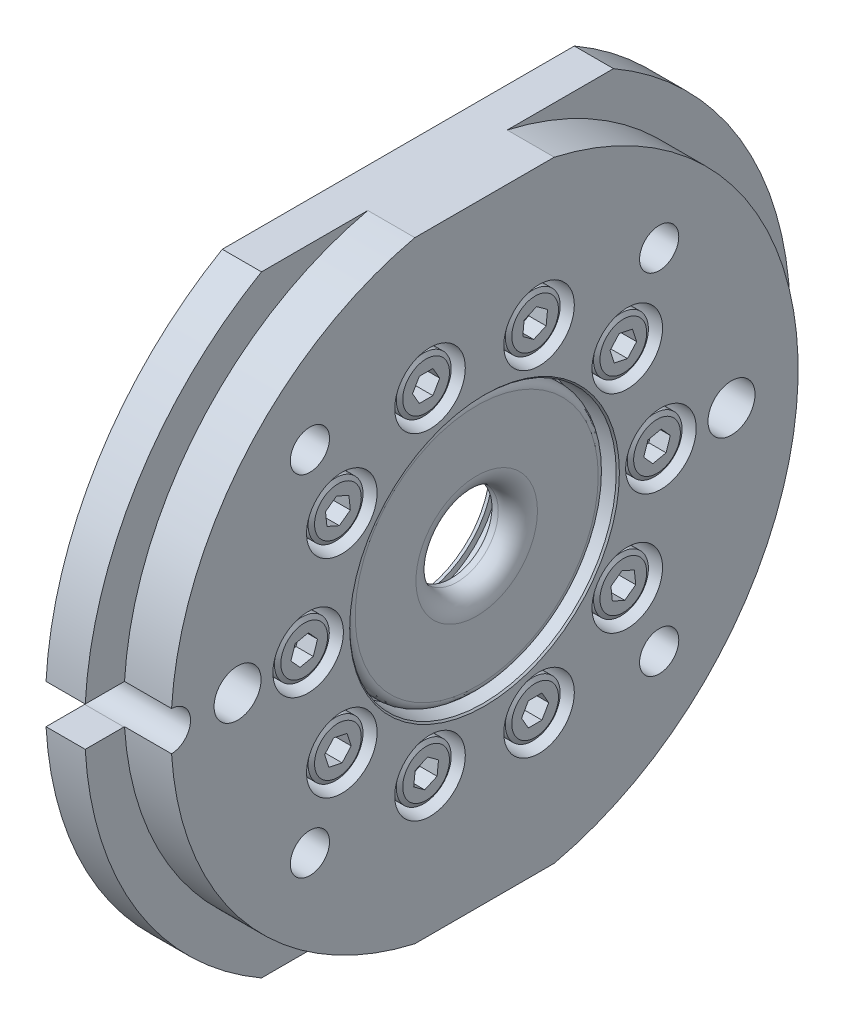
SolidWorks part; units mm, degrees
ref_plane "正面" through (0, 0, 0) normal (0, 0, 1) x (1, 0, 0)
ref_plane "平面" through (0, 0, 0) normal (0, 1, 0) x (1, 0, 0)
ref_plane "右側面" through (0, 0, 0) normal (1, 0, 0) x (0, 0, -1)
ref_plane "平面1" through (503, 0, 0) normal (1, 0, 0) x (0, 0, -1)
sketch "ｽｹｯﾁ1" plane through (503, 0, 0) normal (1, 0, 0) x (0, 0, -1)
  line L0 (-8.8882, 600.5) -> (22.4499, 600.5)
  line L1 (22.4499, 678.5) -> (-8.8882, 678.5)
  arc A0 (22.4499, 600.5) -> (22.4499, 678.5) centre (0, 639.5) ccw
  arc A1 (-8.8882, 678.5) -> (-39.9219, 641.9988) centre (0, 639.5) ccw
  arc A2 (-39.9219, 641.9988) -> (-39.9219, 637.0012) centre (-40, 639.5) cw
  arc A3 (-39.9219, 637.0012) -> (-8.8882, 600.5) centre (0, 639.5) ccw
extrude "ﾎﾞｽ - 押し出し1" add sketch "ｽｹｯﾁ1" against normal blind 6
sketch "ｽｹｯﾁ2" plane through (497, 0, 0) normal (-1, 0, 0) x (0, 0, 1)
  line L0 (-22.4499, 678.5) -> (22.4499, 678.5)
  line L1 (44.9305, 642) -> (40, 642)
  line L2 (40, 637) -> (44.9305, 637)
  line L3 (22.4499, 600.5) -> (-22.4499, 600.5)
  arc A0 (22.4499, 678.5) -> (44.9305, 642) centre (0, 639.5) cw
  arc A1 (40, 642) -> (40, 637) centre (40, 639.5) ccw
  arc A2 (44.9305, 637) -> (22.4499, 600.5) centre (0, 639.5) cw
  arc A3 (-22.4499, 600.5) -> (-22.4499, 678.5) centre (0, 639.5) cw
extrude "ﾎﾞｽ - 押し出し2" add sketch "ｽｹｯﾁ2" along normal blind 5
sketch "ｽｹｯﾁ3" plane through (503, 0, 0) normal (1, 0, 0) x (0, 0, -1)
  line L0 (8.8882, 600.5) -> (22.4499, 600.5)
  line L1 (22.4499, 678.5) -> (8.8882, 678.5)
  arc A0 (8.8882, 678.5) -> (8.8882, 600.5) centre (0, 639.5) cw
  arc A1 (22.4499, 600.5) -> (22.4499, 678.5) centre (0, 639.5) ccw
extrude "ｶｯﾄ - 押し出し1" cut sketch "ｽｹｯﾁ3" against normal blind 6
hole_wizard "M33 ﾍﾘｺｲﾙ用ねじ下穴ﾄﾞﾘﾙ1" positions "ｽｹｯﾁ5" profile "ｽｹｯﾁ4" hole size "M33x3.5" standard "Ansi Metric"
sketch "ｽｹｯﾁ5" plane through (503, 0, 0) normal (1, 0, 0) x (0, 0, -1)
  point P0 (0, 639.5)
sketch "ｽｹｯﾁ4" plane through (503, 639.5, 0) normal (0, 1, 0) x (0, 0, -1)
  line L0 (0, 0) -> (0, 4.5)
  line L1 (0, 4.5) -> (17, 4.5)
  line L2 (17, 4.5) -> (17, 0)
  line L5 (17, 0) -> (0, 0)
  line L10 (0, 4.5) -> (-17, 4.5) construction
  line L11 (0, -6.35) -> (0, 107.95) construction
  dimension "穴の直径" = 34
  dimension "穴の深さ" = 4.5
  dimension "ﾄﾞﾘﾙ角度" = 180
sketch "ｽｹｯﾁ6" plane through (498.5, 0, 0) normal (1, 0, 0) x (0, 0, -1)
  circle A0 centre (0, 639.5) radius 16.5
extrude "ﾎﾞｽ - 押し出し3" add sketch "ｽｹｯﾁ6" along normal blind 3.5
ref_plane "平面2" through (494.4, 0, 0) normal (-1, 0, 0) x (0, -1, 0)
sketch "ｽｹｯﾁ7" plane through (494.4, 0, 0) normal (-1, 0, 0) x (0, -1, 0)
  circle A0 centre (-639.5, 0) radius 10.5
extrude "ｶｯﾄ - 押し出し2" cut sketch "ｽｹｯﾁ7" against normal blind 4.1
sketch "ｽｹｯﾁ8" plane through (498.5, 0, 0) normal (-1, 0, 0) x (0, 0, 1)
  circle A0 centre (0, 639.5) radius 9.7
extrude "ｶｯﾄ - 押し出し3" cut sketch "ｽｹｯﾁ8" against normal blind 0.2
sketch "ｽｹｯﾁ9" plane through (502, 0, 0) normal (1, 0, 0) x (0, 0, -1)
  circle A0 centre (0, 639.5) radius 5.25
extrude "ｶｯﾄ - 押し出し4" cut sketch "ｽｹｯﾁ9" against normal up to next
hole_wizard "M48 すきま穴1" positions "ｽｹｯﾁ11" profile "ｽｹｯﾁ10" hole size "M48" standard "Ansi Metric"
sketch "ｽｹｯﾁ11" plane through (492, 0, 0) normal (-1, 0, 0) x (0, 0, 1)
  point P0 (0, 639.5)
sketch "ｽｹｯﾁ10" plane through (492, 639.5, 0) normal (0, 1, 0) x (0, 0, 1)
  line L0 (0, 0) -> (0, 2)
  line L1 (0, 2) -> (27.5, 2)
  line L2 (27.5, 2) -> (27.5, 0)
  line L5 (27.5, 0) -> (0, 0)
  line L10 (0, 2) -> (-27.5, 2) construction
  line L11 (0, -6.35) -> (0, 107.95) construction
  dimension "穴の直径" = 55
  dimension "穴の深さ" = 2
  dimension "ﾄﾞﾘﾙ角度" = 180
sketch "ｽｹｯﾁ12" plane through (494, 0, 0) normal (-1, 0, 0) x (0, 0, 1)
  circle A0 centre (0, 639.5) radius 9.7
extrude "ｶｯﾄ - 押し出し5" cut sketch "ｽｹｯﾁ12" against normal up to next
hole_wizard "Ø9.0 (9) 直径の穴1" positions "ｽｹｯﾁ14" profile "ｽｹｯﾁ13" hole size "Ø9.0" standard "Ansi Metric"
sketch "ｽｹｯﾁ14" plane through (503, 0, 0) normal (1, 0, 0) x (0, 0, -1)
  point P0 (6.9529, 618.1012)
sketch "ｽｹｯﾁ13" plane through (503, 618.1012, -6.9529) normal (0, 1, 0) x (0, 0, -1)
  line L0 (0, 0) -> (0, 5)
  line L1 (0, 5) -> (4.5, 5)
  line L2 (4.5, 5) -> (4.5, 0)
  line L5 (4.5, 0) -> (0, 0)
  line L10 (0, 5) -> (-4.5, 5) construction
  line L11 (0, -6.35) -> (0, 107.95) construction
  dimension "穴の直径" = 9
  dimension "穴の深さ" = 5
  dimension "ﾄﾞﾘﾙ角度" = 180
sketch "ｽｹｯﾁ15" plane through (498, 0, 0) normal (1, 0, 0) x (0, 0, -1)
  circle A0 centre (6.9529, 618.1012) radius 3.75
extrude "ﾎﾞｽ - 押し出し4" add sketch "ｽｹｯﾁ15" along normal blind 0.5
sketch "ｽｹｯﾁ16" plane through (498.5, 0, 0) normal (1, 0, 0) x (0, 0, -1)
  circle A0 centre (6.9529, 618.1012) radius 3.5
extrude "ﾎﾞｽ - 押し出し5" add sketch "ｽｹｯﾁ16" along normal blind 4
sketch "ｽｹｯﾁ17" plane through (502.5, 0, 0) normal (1, 0, 0) x (0, 0, -1)
  line L0 (8.6849, 618.1012) -> (7.8189, 619.6012)
  line L1 (7.8189, 619.6012) -> (6.0869, 619.6012)
  line L2 (6.0869, 619.6012) -> (5.2208, 618.1012)
  line L3 (5.2208, 618.1012) -> (6.0869, 616.6012)
  line L4 (6.0869, 616.6012) -> (7.8189, 616.6012)
  line L5 (7.8189, 616.6012) -> (8.6849, 618.1012)
extrude "ｶｯﾄ - 押し出し6" cut sketch "ｽｹｯﾁ17" against normal blind 2.2
hole_wizard "Ø9.0 (9) 直径の穴2" positions "ｽｹｯﾁ19" profile "ｽｹｯﾁ18" hole size "Ø9.0" standard "Ansi Metric"
sketch "ｽｹｯﾁ19" plane through (503, 0, 0) normal (1, 0, 0) x (0, 0, -1)
  point P0 (18.2029, 626.2748)
sketch "ｽｹｯﾁ18" plane through (503, 626.2748, -18.2029) normal (0, 1, 0) x (0, 0, -1)
  line L0 (0, 0) -> (0, 5)
  line L1 (0, 5) -> (4.5, 5)
  line L2 (4.5, 5) -> (4.5, 0)
  line L5 (4.5, 0) -> (0, 0)
  line L10 (0, 5) -> (-4.5, 5) construction
  line L11 (0, -6.35) -> (0, 107.95) construction
  dimension "穴の直径" = 9
  dimension "穴の深さ" = 5
  dimension "ﾄﾞﾘﾙ角度" = 180
sketch "ｽｹｯﾁ20" plane through (498, 0, 0) normal (1, 0, 0) x (0, 0, -1)
  circle A0 centre (18.2029, 626.2748) radius 3.75
extrude "ﾎﾞｽ - 押し出し6" add sketch "ｽｹｯﾁ20" along normal blind 0.5
sketch "ｽｹｯﾁ21" plane through (498.5, 0, 0) normal (1, 0, 0) x (0, 0, -1)
  circle A0 centre (18.2029, 626.2748) radius 3.5
extrude "ﾎﾞｽ - 押し出し7" add sketch "ｽｹｯﾁ21" along normal blind 4
sketch "ｽｹｯﾁ22" plane through (502.5, 0, 0) normal (1, 0, 0) x (0, 0, -1)
  line L0 (19.6041, 627.2929) -> (18.0218, 627.9974)
  line L1 (18.0218, 627.9974) -> (16.6206, 626.9793)
  line L2 (16.6206, 626.9793) -> (16.8016, 625.2568)
  line L3 (16.8016, 625.2568) -> (18.3839, 624.5523)
  line L4 (18.3839, 624.5523) -> (19.7852, 625.5703)
  line L5 (19.7852, 625.5703) -> (19.6041, 627.2929)
extrude "ｶｯﾄ - 押し出し7" cut sketch "ｽｹｯﾁ22" against normal blind 2.2
hole_wizard "Ø9.0 (9) 直径の穴3" positions "ｽｹｯﾁ24" profile "ｽｹｯﾁ23" hole size "Ø9.0" standard "Ansi Metric"
sketch "ｽｹｯﾁ24" plane through (503, 0, 0) normal (1, 0, 0) x (0, 0, -1)
  point P0 (22.5, 639.5)
sketch "ｽｹｯﾁ23" plane through (503, 639.5, -22.5) normal (0, 1, 0) x (0, 0, -1)
  line L0 (0, 0) -> (0, 5)
  line L1 (0, 5) -> (4.5, 5)
  line L2 (4.5, 5) -> (4.5, 0)
  line L5 (4.5, 0) -> (0, 0)
  line L10 (0, 5) -> (-4.5, 5) construction
  line L11 (0, -6.35) -> (0, 107.95) construction
  dimension "穴の直径" = 9
  dimension "穴の深さ" = 5
  dimension "ﾄﾞﾘﾙ角度" = 180
sketch "ｽｹｯﾁ25" plane through (498, 0, 0) normal (1, 0, 0) x (0, 0, -1)
  circle A0 centre (22.5, 639.5) radius 3.75
extrude "ﾎﾞｽ - 押し出し8" add sketch "ｽｹｯﾁ25" along normal blind 0.5
sketch "ｽｹｯﾁ26" plane through (498.5, 0, 0) normal (1, 0, 0) x (0, 0, -1)
  circle A0 centre (22.5, 639.5) radius 3.5
extrude "ﾎﾞｽ - 押し出し9" add sketch "ｽｹｯﾁ26" along normal blind 4
sketch "ｽｹｯﾁ27" plane through (502.5, 0, 0) normal (1, 0, 0) x (0, 0, -1)
  line L0 (23.0352, 641.1473) -> (21.341, 640.7872)
  line L1 (21.341, 640.7872) -> (20.8058, 639.1399)
  line L2 (20.8058, 639.1399) -> (21.9648, 637.8527)
  line L3 (21.9648, 637.8527) -> (23.659, 638.2128)
  line L4 (23.659, 638.2128) -> (24.1942, 639.8601)
  line L5 (24.1942, 639.8601) -> (23.0352, 641.1473)
extrude "ｶｯﾄ - 押し出し8" cut sketch "ｽｹｯﾁ27" against normal blind 2.2
hole_wizard "Ø9.0 (9) 直径の穴4" positions "ｽｹｯﾁ29" profile "ｽｹｯﾁ28" hole size "Ø9.0" standard "Ansi Metric"
sketch "ｽｹｯﾁ29" plane through (503, 0, 0) normal (1, 0, 0) x (0, 0, -1)
  point P0 (18.2029, 652.7252)
sketch "ｽｹｯﾁ28" plane through (503, 652.7252, -18.2029) normal (0, 1, 0) x (0, 0, -1)
  line L0 (0, 0) -> (0, 5)
  line L1 (0, 5) -> (4.5, 5)
  line L2 (4.5, 5) -> (4.5, 0)
  line L5 (4.5, 0) -> (0, 0)
  line L10 (0, 5) -> (-4.5, 5) construction
  line L11 (0, -6.35) -> (0, 107.95) construction
  dimension "穴の直径" = 9
  dimension "穴の深さ" = 5
  dimension "ﾄﾞﾘﾙ角度" = 180
sketch "ｽｹｯﾁ30" plane through (498, 0, 0) normal (1, 0, 0) x (0, 0, -1)
  circle A0 centre (18.2029, 652.7252) radius 3.75
extrude "ﾎﾞｽ - 押し出し10" add sketch "ｽｹｯﾁ30" along normal blind 0.5
sketch "ｽｹｯﾁ31" plane through (498.5, 0, 0) normal (1, 0, 0) x (0, 0, -1)
  circle A0 centre (18.2029, 652.7252) radius 3.5
extrude "ﾎﾞｽ - 押し出し11" add sketch "ｽｹｯﾁ31" along normal blind 4
sketch "ｽｹｯﾁ32" plane through (502.5, 0, 0) normal (1, 0, 0) x (0, 0, -1)
  line L0 (17.6676, 654.3724) -> (16.5087, 653.0853)
  line L1 (16.5087, 653.0853) -> (17.0439, 651.438)
  line L2 (17.0439, 651.438) -> (18.7381, 651.0779)
  line L3 (18.7381, 651.0779) -> (19.8971, 652.3651)
  line L4 (19.8971, 652.3651) -> (19.3619, 654.0123)
  line L5 (19.3619, 654.0123) -> (17.6676, 654.3724)
extrude "ｶｯﾄ - 押し出し9" cut sketch "ｽｹｯﾁ32" against normal blind 2.2
hole_wizard "Ø9.0 (9) 直径の穴5" positions "ｽｹｯﾁ34" profile "ｽｹｯﾁ33" hole size "Ø9.0" standard "Ansi Metric"
sketch "ｽｹｯﾁ34" plane through (503, 0, 0) normal (1, 0, 0) x (0, 0, -1)
  point P0 (6.9529, 660.8988)
sketch "ｽｹｯﾁ33" plane through (503, 660.8988, -6.9529) normal (0, 1, 0) x (0, 0, -1)
  line L0 (0, 0) -> (0, 5)
  line L1 (0, 5) -> (4.5, 5)
  line L2 (4.5, 5) -> (4.5, 0)
  line L5 (4.5, 0) -> (0, 0)
  line L10 (0, 5) -> (-4.5, 5) construction
  line L11 (0, -6.35) -> (0, 107.95) construction
  dimension "穴の直径" = 9
  dimension "穴の深さ" = 5
  dimension "ﾄﾞﾘﾙ角度" = 180
sketch "ｽｹｯﾁ35" plane through (498, 0, 0) normal (1, 0, 0) x (0, 0, -1)
  circle A0 centre (6.9529, 660.8988) radius 3.75
extrude "ﾎﾞｽ - 押し出し12" add sketch "ｽｹｯﾁ35" along normal blind 0.5
sketch "ｽｹｯﾁ36" plane through (498.5, 0, 0) normal (1, 0, 0) x (0, 0, -1)
  circle A0 centre (6.9529, 660.8988) radius 3.5
extrude "ﾎﾞｽ - 押し出し13" add sketch "ｽｹｯﾁ36" along normal blind 4
sketch "ｽｹｯﾁ37" plane through (502.5, 0, 0) normal (1, 0, 0) x (0, 0, -1)
  line L0 (5.5516, 661.9168) -> (5.3706, 660.1943)
  line L1 (5.3706, 660.1943) -> (6.7718, 659.1762)
  line L2 (6.7718, 659.1762) -> (8.3541, 659.8807)
  line L3 (8.3541, 659.8807) -> (8.5352, 661.6033)
  line L4 (8.5352, 661.6033) -> (7.1339, 662.6213)
  line L5 (7.1339, 662.6213) -> (5.5516, 661.9168)
extrude "ｶｯﾄ - 押し出し10" cut sketch "ｽｹｯﾁ37" against normal blind 2.2
hole_wizard "Ø9.0 (9) 直径の穴6" positions "ｽｹｯﾁ39" profile "ｽｹｯﾁ38" hole size "Ø9.0" standard "Ansi Metric"
sketch "ｽｹｯﾁ39" plane through (503, 0, 0) normal (1, 0, 0) x (0, 0, -1)
  point P0 (-6.9529, 660.8988)
sketch "ｽｹｯﾁ38" plane through (503, 660.8988, 6.9529) normal (0, 1, 0) x (0, 0, -1)
  line L0 (0, 0) -> (0, 5)
  line L1 (0, 5) -> (4.5, 5)
  line L2 (4.5, 5) -> (4.5, 0)
  line L5 (4.5, 0) -> (0, 0)
  line L10 (0, 5) -> (-4.5, 5) construction
  line L11 (0, -6.35) -> (0, 107.95) construction
  dimension "穴の直径" = 9
  dimension "穴の深さ" = 5
  dimension "ﾄﾞﾘﾙ角度" = 180
sketch "ｽｹｯﾁ40" plane through (498, 0, 0) normal (1, 0, 0) x (0, 0, -1)
  circle A0 centre (-6.9529, 660.8988) radius 3.75
extrude "ﾎﾞｽ - 押し出し14" add sketch "ｽｹｯﾁ40" along normal blind 0.5
sketch "ｽｹｯﾁ41" plane through (498.5, 0, 0) normal (1, 0, 0) x (0, 0, -1)
  circle A0 centre (-6.9529, 660.8988) radius 3.5
extrude "ﾎﾞｽ - 押し出し15" add sketch "ｽｹｯﾁ41" along normal blind 4
sketch "ｽｹｯﾁ42" plane through (502.5, 0, 0) normal (1, 0, 0) x (0, 0, -1)
  line L0 (-8.6849, 660.8988) -> (-7.8189, 659.3988)
  line L1 (-7.8189, 659.3988) -> (-6.0869, 659.3988)
  line L2 (-6.0869, 659.3988) -> (-5.2208, 660.8988)
  line L3 (-5.2208, 660.8988) -> (-6.0869, 662.3988)
  line L4 (-6.0869, 662.3988) -> (-7.8189, 662.3988)
  line L5 (-7.8189, 662.3988) -> (-8.6849, 660.8988)
extrude "ｶｯﾄ - 押し出し11" cut sketch "ｽｹｯﾁ42" against normal blind 2.2
hole_wizard "Ø9.0 (9) 直径の穴7" positions "ｽｹｯﾁ44" profile "ｽｹｯﾁ43" hole size "Ø9.0" standard "Ansi Metric"
sketch "ｽｹｯﾁ44" plane through (503, 0, 0) normal (1, 0, 0) x (0, 0, -1)
  point P0 (-18.2029, 652.7252)
sketch "ｽｹｯﾁ43" plane through (503, 652.7252, 18.2029) normal (0, 1, 0) x (0, 0, -1)
  line L0 (0, 0) -> (0, 5)
  line L1 (0, 5) -> (4.5, 5)
  line L2 (4.5, 5) -> (4.5, 0)
  line L5 (4.5, 0) -> (0, 0)
  line L10 (0, 5) -> (-4.5, 5) construction
  line L11 (0, -6.35) -> (0, 107.95) construction
  dimension "穴の直径" = 9
  dimension "穴の深さ" = 5
  dimension "ﾄﾞﾘﾙ角度" = 180
sketch "ｽｹｯﾁ45" plane through (498, 0, 0) normal (1, 0, 0) x (0, 0, -1)
  circle A0 centre (-18.2029, 652.7252) radius 3.75
extrude "ﾎﾞｽ - 押し出し16" add sketch "ｽｹｯﾁ45" along normal blind 0.5
sketch "ｽｹｯﾁ46" plane through (498.5, 0, 0) normal (1, 0, 0) x (0, 0, -1)
  circle A0 centre (-18.2029, 652.7252) radius 3.5
extrude "ﾎﾞｽ - 押し出し17" add sketch "ｽｹｯﾁ46" along normal blind 4
sketch "ｽｹｯﾁ47" plane through (502.5, 0, 0) normal (1, 0, 0) x (0, 0, -1)
  line L0 (-19.6041, 651.7071) -> (-18.0218, 651.0026)
  line L1 (-18.0218, 651.0026) -> (-16.6206, 652.0207)
  line L2 (-16.6206, 652.0207) -> (-16.8016, 653.7432)
  line L3 (-16.8016, 653.7432) -> (-18.3839, 654.4477)
  line L4 (-18.3839, 654.4477) -> (-19.7852, 653.4297)
  line L5 (-19.7852, 653.4297) -> (-19.6041, 651.7071)
extrude "ｶｯﾄ - 押し出し12" cut sketch "ｽｹｯﾁ47" against normal blind 2.2
hole_wizard "Ø9.0 (9) 直径の穴8" positions "ｽｹｯﾁ49" profile "ｽｹｯﾁ48" hole size "Ø9.0" standard "Ansi Metric"
sketch "ｽｹｯﾁ49" plane through (503, 0, 0) normal (1, 0, 0) x (0, 0, -1)
  point P0 (-22.5, 639.5)
sketch "ｽｹｯﾁ48" plane through (503, 639.5, 22.5) normal (0, 1, 0) x (0, 0, -1)
  line L0 (0, 0) -> (0, 5)
  line L1 (0, 5) -> (4.5, 5)
  line L2 (4.5, 5) -> (4.5, 0)
  line L5 (4.5, 0) -> (0, 0)
  line L10 (0, 5) -> (-4.5, 5) construction
  line L11 (0, -6.35) -> (0, 107.95) construction
  dimension "穴の直径" = 9
  dimension "穴の深さ" = 5
  dimension "ﾄﾞﾘﾙ角度" = 180
sketch "ｽｹｯﾁ50" plane through (498, 0, 0) normal (1, 0, 0) x (0, 0, -1)
  circle A0 centre (-22.5, 639.5) radius 3.75
extrude "ﾎﾞｽ - 押し出し18" add sketch "ｽｹｯﾁ50" along normal blind 0.5
sketch "ｽｹｯﾁ51" plane through (498.5, 0, 0) normal (1, 0, 0) x (0, 0, -1)
  circle A0 centre (-22.5, 639.5) radius 3.5
extrude "ﾎﾞｽ - 押し出し19" add sketch "ｽｹｯﾁ51" along normal blind 4
sketch "ｽｹｯﾁ52" plane through (502.5, 0, 0) normal (1, 0, 0) x (0, 0, -1)
  line L0 (-23.0352, 637.8527) -> (-21.341, 638.2128)
  line L1 (-21.341, 638.2128) -> (-20.8058, 639.8601)
  line L2 (-20.8058, 639.8601) -> (-21.9648, 641.1473)
  line L3 (-21.9648, 641.1473) -> (-23.659, 640.7872)
  line L4 (-23.659, 640.7872) -> (-24.1942, 639.1399)
  line L5 (-24.1942, 639.1399) -> (-23.0352, 637.8527)
extrude "ｶｯﾄ - 押し出し13" cut sketch "ｽｹｯﾁ52" against normal blind 2.2
hole_wizard "Ø9.0 (9) 直径の穴9" positions "ｽｹｯﾁ54" profile "ｽｹｯﾁ53" hole size "Ø9.0" standard "Ansi Metric"
sketch "ｽｹｯﾁ54" plane through (503, 0, 0) normal (1, 0, 0) x (0, 0, -1)
  point P0 (-18.2029, 626.2748)
sketch "ｽｹｯﾁ53" plane through (503, 626.2748, 18.2029) normal (0, 1, 0) x (0, 0, -1)
  line L0 (0, 0) -> (0, 5)
  line L1 (0, 5) -> (4.5, 5)
  line L2 (4.5, 5) -> (4.5, 0)
  line L5 (4.5, 0) -> (0, 0)
  line L10 (0, 5) -> (-4.5, 5) construction
  line L11 (0, -6.35) -> (0, 107.95) construction
  dimension "穴の直径" = 9
  dimension "穴の深さ" = 5
  dimension "ﾄﾞﾘﾙ角度" = 180
sketch "ｽｹｯﾁ55" plane through (498, 0, 0) normal (1, 0, 0) x (0, 0, -1)
  circle A0 centre (-18.2029, 626.2748) radius 3.75
extrude "ﾎﾞｽ - 押し出し20" add sketch "ｽｹｯﾁ55" along normal blind 0.5
sketch "ｽｹｯﾁ56" plane through (498.5, 0, 0) normal (1, 0, 0) x (0, 0, -1)
  circle A0 centre (-18.2029, 626.2748) radius 3.5
extrude "ﾎﾞｽ - 押し出し21" add sketch "ｽｹｯﾁ56" along normal blind 4
sketch "ｽｹｯﾁ57" plane through (502.5, 0, 0) normal (1, 0, 0) x (0, 0, -1)
  line L0 (-17.6676, 624.6276) -> (-16.5087, 625.9147)
  line L1 (-16.5087, 625.9147) -> (-17.0439, 627.562)
  line L2 (-17.0439, 627.562) -> (-18.7381, 627.9221)
  line L3 (-18.7381, 627.9221) -> (-19.8971, 626.6349)
  line L4 (-19.8971, 626.6349) -> (-19.3619, 624.9877)
  line L5 (-19.3619, 624.9877) -> (-17.6676, 624.6276)
extrude "ｶｯﾄ - 押し出し14" cut sketch "ｽｹｯﾁ57" against normal blind 2.2
hole_wizard "Ø9.0 (9) 直径の穴10" positions "ｽｹｯﾁ59" profile "ｽｹｯﾁ58" hole size "Ø9.0" standard "Ansi Metric"
sketch "ｽｹｯﾁ59" plane through (503, 0, 0) normal (1, 0, 0) x (0, 0, -1)
  point P0 (-6.9529, 618.1012)
sketch "ｽｹｯﾁ58" plane through (503, 618.1012, 6.9529) normal (0, 1, 0) x (0, 0, -1)
  line L0 (0, 0) -> (0, 5)
  line L1 (0, 5) -> (4.5, 5)
  line L2 (4.5, 5) -> (4.5, 0)
  line L5 (4.5, 0) -> (0, 0)
  line L10 (0, 5) -> (-4.5, 5) construction
  line L11 (0, -6.35) -> (0, 107.95) construction
  dimension "穴の直径" = 9
  dimension "穴の深さ" = 5
  dimension "ﾄﾞﾘﾙ角度" = 180
sketch "ｽｹｯﾁ60" plane through (498, 0, 0) normal (1, 0, 0) x (0, 0, -1)
  circle A0 centre (-6.9529, 618.1012) radius 3.75
extrude "ﾎﾞｽ - 押し出し22" add sketch "ｽｹｯﾁ60" along normal blind 0.5
sketch "ｽｹｯﾁ61" plane through (498.5, 0, 0) normal (1, 0, 0) x (0, 0, -1)
  circle A0 centre (-6.9529, 618.1012) radius 3.5
extrude "ﾎﾞｽ - 押し出し23" add sketch "ｽｹｯﾁ61" along normal blind 4
sketch "ｽｹｯﾁ62" plane through (502.5, 0, 0) normal (1, 0, 0) x (0, 0, -1)
  line L0 (-5.5516, 617.0832) -> (-5.3706, 618.8057)
  line L1 (-5.3706, 618.8057) -> (-6.7718, 619.8238)
  line L2 (-6.7718, 619.8238) -> (-8.3541, 619.1193)
  line L3 (-8.3541, 619.1193) -> (-8.5352, 617.3967)
  line L4 (-8.5352, 617.3967) -> (-7.1339, 616.3787)
  line L5 (-7.1339, 616.3787) -> (-5.5516, 617.0832)
extrude "ｶｯﾄ - 押し出し15" cut sketch "ｽｹｯﾁ62" against normal blind 2.2
hole_wizard "Ø4.3 (4.3) 直径の穴1" positions "ｽｹｯﾁ64" profile "ｽｹｯﾁ63" hole size "Ø4.3" standard "Ansi Metric"
sketch "ｽｹｯﾁ64" plane through (494, 0, 0) normal (-1, 0, 0) x (0, 0, 1)
  point P0 (-6.9529, 618.1012)
sketch "ｽｹｯﾁ63" plane through (494, 618.1012, -6.9529) normal (0, 1, 0) x (0, 0, 1)
  line L0 (0, 0) -> (0, 4.5)
  line L1 (0, 4.5) -> (2.15, 4.5)
  line L2 (2.15, 4.5) -> (2.15, 0)
  line L5 (2.15, 0) -> (0, 0)
  line L10 (0, 4.5) -> (-2.15, 4.5) construction
  line L11 (0, -6.35) -> (0, 107.95) construction
  dimension "穴の直径" = 4.3
  dimension "穴の深さ" = 4.5
  dimension "ﾄﾞﾘﾙ角度" = 180
hole_wizard "Ø4.3 (4.3) 直径の穴2" positions "ｽｹｯﾁ66" profile "ｽｹｯﾁ65" hole size "Ø4.3" standard "Ansi Metric"
sketch "ｽｹｯﾁ66" plane through (494, 0, 0) normal (-1, 0, 0) x (0, 0, 1)
  point P0 (-18.2029, 626.2748)
sketch "ｽｹｯﾁ65" plane through (494, 626.2748, -18.2029) normal (0, 1, 0) x (0, 0, 1)
  line L0 (0, 0) -> (0, 4.5)
  line L1 (0, 4.5) -> (2.15, 4.5)
  line L2 (2.15, 4.5) -> (2.15, 0)
  line L5 (2.15, 0) -> (0, 0)
  line L10 (0, 4.5) -> (-2.15, 4.5) construction
  line L11 (0, -6.35) -> (0, 107.95) construction
  dimension "穴の直径" = 4.3
  dimension "穴の深さ" = 4.5
  dimension "ﾄﾞﾘﾙ角度" = 180
hole_wizard "Ø4.3 (4.3) 直径の穴3" positions "ｽｹｯﾁ68" profile "ｽｹｯﾁ67" hole size "Ø4.3" standard "Ansi Metric"
sketch "ｽｹｯﾁ68" plane through (494, 0, 0) normal (-1, 0, 0) x (0, 0, 1)
  point P0 (-22.5, 639.5)
sketch "ｽｹｯﾁ67" plane through (494, 639.5, -22.5) normal (0, 1, 0) x (0, 0, 1)
  line L0 (0, 0) -> (0, 4.5)
  line L1 (0, 4.5) -> (2.15, 4.5)
  line L2 (2.15, 4.5) -> (2.15, 0)
  line L5 (2.15, 0) -> (0, 0)
  line L10 (0, 4.5) -> (-2.15, 4.5) construction
  line L11 (0, -6.35) -> (0, 107.95) construction
  dimension "穴の直径" = 4.3
  dimension "穴の深さ" = 4.5
  dimension "ﾄﾞﾘﾙ角度" = 180
hole_wizard "Ø4.3 (4.3) 直径の穴4" positions "ｽｹｯﾁ70" profile "ｽｹｯﾁ69" hole size "Ø4.3" standard "Ansi Metric"
sketch "ｽｹｯﾁ70" plane through (494, 0, 0) normal (-1, 0, 0) x (0, 0, 1)
  point P0 (-18.2029, 652.7252)
sketch "ｽｹｯﾁ69" plane through (494, 652.7252, -18.2029) normal (0, 1, 0) x (0, 0, 1)
  line L0 (0, 0) -> (0, 4.5)
  line L1 (0, 4.5) -> (2.15, 4.5)
  line L2 (2.15, 4.5) -> (2.15, 0)
  line L5 (2.15, 0) -> (0, 0)
  line L10 (0, 4.5) -> (-2.15, 4.5) construction
  line L11 (0, -6.35) -> (0, 107.95) construction
  dimension "穴の直径" = 4.3
  dimension "穴の深さ" = 4.5
  dimension "ﾄﾞﾘﾙ角度" = 180
hole_wizard "Ø4.3 (4.3) 直径の穴5" positions "ｽｹｯﾁ72" profile "ｽｹｯﾁ71" hole size "Ø4.3" standard "Ansi Metric"
sketch "ｽｹｯﾁ72" plane through (494, 0, 0) normal (-1, 0, 0) x (0, 0, 1)
  point P0 (-6.9529, 660.8988)
sketch "ｽｹｯﾁ71" plane through (494, 660.8988, -6.9529) normal (0, 1, 0) x (0, 0, 1)
  line L0 (0, 0) -> (0, 4.5)
  line L1 (0, 4.5) -> (2.15, 4.5)
  line L2 (2.15, 4.5) -> (2.15, 0)
  line L5 (2.15, 0) -> (0, 0)
  line L10 (0, 4.5) -> (-2.15, 4.5) construction
  line L11 (0, -6.35) -> (0, 107.95) construction
  dimension "穴の直径" = 4.3
  dimension "穴の深さ" = 4.5
  dimension "ﾄﾞﾘﾙ角度" = 180
hole_wizard "Ø4.3 (4.3) 直径の穴6" positions "ｽｹｯﾁ74" profile "ｽｹｯﾁ73" hole size "Ø4.3" standard "Ansi Metric"
sketch "ｽｹｯﾁ74" plane through (494, 0, 0) normal (-1, 0, 0) x (0, 0, 1)
  point P0 (6.9529, 660.8988)
sketch "ｽｹｯﾁ73" plane through (494, 660.8988, 6.9529) normal (0, 1, 0) x (0, 0, 1)
  line L0 (0, 0) -> (0, 4.5)
  line L1 (0, 4.5) -> (2.15, 4.5)
  line L2 (2.15, 4.5) -> (2.15, 0)
  line L5 (2.15, 0) -> (0, 0)
  line L10 (0, 4.5) -> (-2.15, 4.5) construction
  line L11 (0, -6.35) -> (0, 107.95) construction
  dimension "穴の直径" = 4.3
  dimension "穴の深さ" = 4.5
  dimension "ﾄﾞﾘﾙ角度" = 180
hole_wizard "Ø4.3 (4.3) 直径の穴7" positions "ｽｹｯﾁ76" profile "ｽｹｯﾁ75" hole size "Ø4.3" standard "Ansi Metric"
sketch "ｽｹｯﾁ76" plane through (494, 0, 0) normal (-1, 0, 0) x (0, 0, 1)
  point P0 (18.2029, 652.7252)
sketch "ｽｹｯﾁ75" plane through (494, 652.7252, 18.2029) normal (0, 1, 0) x (0, 0, 1)
  line L0 (0, 0) -> (0, 4.5)
  line L1 (0, 4.5) -> (2.15, 4.5)
  line L2 (2.15, 4.5) -> (2.15, 0)
  line L5 (2.15, 0) -> (0, 0)
  line L10 (0, 4.5) -> (-2.15, 4.5) construction
  line L11 (0, -6.35) -> (0, 107.95) construction
  dimension "穴の直径" = 4.3
  dimension "穴の深さ" = 4.5
  dimension "ﾄﾞﾘﾙ角度" = 180
hole_wizard "Ø4.3 (4.3) 直径の穴8" positions "ｽｹｯﾁ78" profile "ｽｹｯﾁ77" hole size "Ø4.3" standard "Ansi Metric"
sketch "ｽｹｯﾁ78" plane through (494, 0, 0) normal (-1, 0, 0) x (0, 0, 1)
  point P0 (22.5, 639.5)
sketch "ｽｹｯﾁ77" plane through (494, 639.5, 22.5) normal (0, 1, 0) x (0, 0, 1)
  line L0 (0, 0) -> (0, 4.5)
  line L1 (0, 4.5) -> (2.15, 4.5)
  line L2 (2.15, 4.5) -> (2.15, 0)
  line L5 (2.15, 0) -> (0, 0)
  line L10 (0, 4.5) -> (-2.15, 4.5) construction
  line L11 (0, -6.35) -> (0, 107.95) construction
  dimension "穴の直径" = 4.3
  dimension "穴の深さ" = 4.5
  dimension "ﾄﾞﾘﾙ角度" = 180
hole_wizard "Ø4.3 (4.3) 直径の穴9" positions "ｽｹｯﾁ80" profile "ｽｹｯﾁ79" hole size "Ø4.3" standard "Ansi Metric"
sketch "ｽｹｯﾁ80" plane through (494, 0, 0) normal (-1, 0, 0) x (0, 0, 1)
  point P0 (18.2029, 626.2748)
sketch "ｽｹｯﾁ79" plane through (494, 626.2748, 18.2029) normal (0, 1, 0) x (0, 0, 1)
  line L0 (0, 0) -> (0, 4.5)
  line L1 (0, 4.5) -> (2.15, 4.5)
  line L2 (2.15, 4.5) -> (2.15, 0)
  line L5 (2.15, 0) -> (0, 0)
  line L10 (0, 4.5) -> (-2.15, 4.5) construction
  line L11 (0, -6.35) -> (0, 107.95) construction
  dimension "穴の直径" = 4.3
  dimension "穴の深さ" = 4.5
  dimension "ﾄﾞﾘﾙ角度" = 180
hole_wizard "Ø4.3 (4.3) 直径の穴10" positions "ｽｹｯﾁ82" profile "ｽｹｯﾁ81" hole size "Ø4.3" standard "Ansi Metric"
sketch "ｽｹｯﾁ82" plane through (494, 0, 0) normal (-1, 0, 0) x (0, 0, 1)
  point P0 (6.9529, 618.1012)
sketch "ｽｹｯﾁ81" plane through (494, 618.1012, 6.9529) normal (0, 1, 0) x (0, 0, 1)
  line L0 (0, 0) -> (0, 4.5)
  line L1 (0, 4.5) -> (2.15, 4.5)
  line L2 (2.15, 4.5) -> (2.15, 0)
  line L5 (2.15, 0) -> (0, 0)
  line L10 (0, 4.5) -> (-2.15, 4.5) construction
  line L11 (0, -6.35) -> (0, 107.95) construction
  dimension "穴の直径" = 4.3
  dimension "穴の深さ" = 4.5
  dimension "ﾄﾞﾘﾙ角度" = 180
ref_plane "平面3" through (0, 0, 6.9529) normal (0, 0, -1) x (-1, 0, 0)
sketch "ｽｹｯﾁ83" plane through (0, 0, 6.9529) normal (0, 0, -1) x (-1, 0, 0)
  line L0 (-498.5, 620.1012) -> (-498.5, 618.1012)
  line L1 (-498.5, 618.1012) -> (-494, 618.1012)
  line L2 (-494, 618.1012) -> (-494, 620.1012)
  line L3 (-494, 620.1012) -> (-498.5, 620.1012)
  line L4 (-498.5, 618.1012) -> (-494, 618.1012) construction
revolve "回転1" add sketch "ｽｹｯﾁ83" angle 360 about L4 reverse direction yes
ref_plane "平面4" through (0, 0, 18.2029) normal (0, 0, -1) x (-1, 0, 0)
sketch "ｽｹｯﾁ84" plane through (0, 0, 18.2029) normal (0, 0, -1) x (-1, 0, 0)
  line L0 (-498.5, 628.2748) -> (-498.5, 626.2748)
  line L1 (-498.5, 626.2748) -> (-494, 626.2748)
  line L2 (-494, 626.2748) -> (-494, 628.2748)
  line L3 (-494, 628.2748) -> (-498.5, 628.2748)
  line L4 (-498.5, 626.2748) -> (-494, 626.2748) construction
revolve "回転2" add sketch "ｽｹｯﾁ84" angle 360 about L4 reverse direction yes
ref_plane "平面5" through (0, 0, 22.5) normal (0, 0, -1) x (-1, 0, 0)
sketch "ｽｹｯﾁ85" plane through (0, 0, 22.5) normal (0, 0, -1) x (-1, 0, 0)
  line L0 (-498.5, 641.5) -> (-498.5, 639.5)
  line L1 (-498.5, 639.5) -> (-494, 639.5)
  line L2 (-494, 639.5) -> (-494, 641.5)
  line L3 (-494, 641.5) -> (-498.5, 641.5)
  line L4 (-498.5, 639.5) -> (-494, 639.5) construction
revolve "回転3" add sketch "ｽｹｯﾁ85" angle 360 about L4 reverse direction yes
sketch "ｽｹｯﾁ86" plane through (0, 0, 18.2029) normal (0, 0, -1) x (-1, 0, 0)
  line L0 (-498.5, 654.7252) -> (-498.5, 652.7252)
  line L1 (-498.5, 652.7252) -> (-494, 652.7252)
  line L2 (-494, 652.7252) -> (-494, 654.7252)
  line L3 (-494, 654.7252) -> (-498.5, 654.7252)
  line L4 (-498.5, 652.7252) -> (-494, 652.7252) construction
revolve "回転4" add sketch "ｽｹｯﾁ86" angle 360 about L4 reverse direction yes
sketch "ｽｹｯﾁ87" plane through (0, 0, 6.9529) normal (0, 0, -1) x (-1, 0, 0)
  line L0 (-498.5, 662.8988) -> (-498.5, 660.8988)
  line L1 (-498.5, 660.8988) -> (-494, 660.8988)
  line L2 (-494, 660.8988) -> (-494, 662.8988)
  line L3 (-494, 662.8988) -> (-498.5, 662.8988)
  line L4 (-498.5, 660.8988) -> (-494, 660.8988) construction
revolve "回転5" add sketch "ｽｹｯﾁ87" angle 360 about L4 reverse direction yes
ref_plane "平面6" through (0, 0, -6.9529) normal (0, 0, -1) x (-1, 0, 0)
sketch "ｽｹｯﾁ88" plane through (0, 0, -6.9529) normal (0, 0, -1) x (-1, 0, 0)
  line L0 (-498.5, 662.8988) -> (-498.5, 660.8988)
  line L1 (-498.5, 660.8988) -> (-494, 660.8988)
  line L2 (-494, 660.8988) -> (-494, 662.8988)
  line L3 (-494, 662.8988) -> (-498.5, 662.8988)
  line L4 (-498.5, 660.8988) -> (-494, 660.8988) construction
revolve "回転6" add sketch "ｽｹｯﾁ88" angle 360 about L4 reverse direction yes
ref_plane "平面7" through (0, 0, -18.2029) normal (0, 0, -1) x (-1, 0, 0)
sketch "ｽｹｯﾁ89" plane through (0, 0, -18.2029) normal (0, 0, -1) x (-1, 0, 0)
  line L0 (-498.5, 654.7252) -> (-498.5, 652.7252)
  line L1 (-498.5, 652.7252) -> (-494, 652.7252)
  line L2 (-494, 652.7252) -> (-494, 654.7252)
  line L3 (-494, 654.7252) -> (-498.5, 654.7252)
  line L4 (-498.5, 652.7252) -> (-494, 652.7252) construction
revolve "回転7" add sketch "ｽｹｯﾁ89" angle 360 about L4 reverse direction yes
ref_plane "平面8" through (0, 0, -22.5) normal (0, 0, -1) x (-1, 0, 0)
sketch "ｽｹｯﾁ90" plane through (0, 0, -22.5) normal (0, 0, -1) x (-1, 0, 0)
  line L0 (-498.5, 641.5) -> (-498.5, 639.5)
  line L1 (-498.5, 639.5) -> (-494, 639.5)
  line L2 (-494, 639.5) -> (-494, 641.5)
  line L3 (-494, 641.5) -> (-498.5, 641.5)
  line L4 (-498.5, 639.5) -> (-494, 639.5) construction
revolve "回転8" add sketch "ｽｹｯﾁ90" angle 360 about L4 reverse direction yes
sketch "ｽｹｯﾁ91" plane through (0, 0, -18.2029) normal (0, 0, -1) x (-1, 0, 0)
  line L0 (-498.5, 628.2748) -> (-498.5, 626.2748)
  line L1 (-498.5, 626.2748) -> (-494, 626.2748)
  line L2 (-494, 626.2748) -> (-494, 628.2748)
  line L3 (-494, 628.2748) -> (-498.5, 628.2748)
  line L4 (-498.5, 626.2748) -> (-494, 626.2748) construction
revolve "回転9" add sketch "ｽｹｯﾁ91" angle 360 about L4 reverse direction yes
sketch "ｽｹｯﾁ92" plane through (0, 0, -6.9529) normal (0, 0, -1) x (-1, 0, 0)
  line L0 (-498.5, 620.1012) -> (-498.5, 618.1012)
  line L1 (-498.5, 618.1012) -> (-494, 618.1012)
  line L2 (-494, 618.1012) -> (-494, 620.1012)
  line L3 (-494, 620.1012) -> (-498.5, 620.1012)
  line L4 (-498.5, 618.1012) -> (-494, 618.1012) construction
revolve "回転10" add sketch "ｽｹｯﾁ92" angle 360 about L4 reverse direction yes
sketch "ｽｹｯﾁ93" plane through (0, 0, 6.9529) normal (0, 0, -1) x (-1, 0, 0)
  line L0 (-494, 620.2512) -> (-494, 620.3512)
  line L1 (-494, 620.3512) -> (-498, 620.3512)
  line L2 (-498, 620.3512) -> (-498, 620.2512)
  line L3 (-498, 620.2512) -> (-494, 620.2512)
  line L4 (-498, 618.1012) -> (-494, 618.1012) construction
revolve "ｶｯﾄ - 回転1" cut sketch "ｽｹｯﾁ93" angle 360 about L4 reverse direction yes
sketch "ｽｹｯﾁ94" plane through (0, 0, 18.2029) normal (0, 0, -1) x (-1, 0, 0)
  line L0 (-494, 628.4248) -> (-494, 628.5248)
  line L1 (-494, 628.5248) -> (-498, 628.5248)
  line L2 (-498, 628.5248) -> (-498, 628.4248)
  line L3 (-498, 628.4248) -> (-494, 628.4248)
  line L4 (-498, 626.2748) -> (-494, 626.2748) construction
revolve "ｶｯﾄ - 回転2" cut sketch "ｽｹｯﾁ94" angle 360 about L4 reverse direction yes
sketch "ｽｹｯﾁ95" plane through (0, 0, 22.5) normal (0, 0, -1) x (-1, 0, 0)
  line L0 (-494, 641.65) -> (-494, 641.75)
  line L1 (-494, 641.75) -> (-498, 641.75)
  line L2 (-498, 641.75) -> (-498, 641.65)
  line L3 (-498, 641.65) -> (-494, 641.65)
  line L4 (-498, 639.5) -> (-494, 639.5) construction
revolve "ｶｯﾄ - 回転3" cut sketch "ｽｹｯﾁ95" angle 360 about L4 reverse direction yes
sketch "ｽｹｯﾁ96" plane through (0, 0, 18.2029) normal (0, 0, -1) x (-1, 0, 0)
  line L0 (-494, 654.8752) -> (-494, 654.9752)
  line L1 (-494, 654.9752) -> (-498, 654.9752)
  line L2 (-498, 654.9752) -> (-498, 654.8752)
  line L3 (-498, 654.8752) -> (-494, 654.8752)
  line L4 (-498, 652.7252) -> (-494, 652.7252) construction
revolve "ｶｯﾄ - 回転4" cut sketch "ｽｹｯﾁ96" angle 360 about L4 reverse direction yes
sketch "ｽｹｯﾁ97" plane through (0, 0, 6.9529) normal (0, 0, -1) x (-1, 0, 0)
  line L0 (-494, 663.0488) -> (-494, 663.1488)
  line L1 (-494, 663.1488) -> (-498, 663.1488)
  line L2 (-498, 663.1488) -> (-498, 663.0488)
  line L3 (-498, 663.0488) -> (-494, 663.0488)
  line L4 (-498, 660.8988) -> (-494, 660.8988) construction
revolve "ｶｯﾄ - 回転5" cut sketch "ｽｹｯﾁ97" angle 360 about L4 reverse direction yes
sketch "ｽｹｯﾁ98" plane through (0, 0, -6.9529) normal (0, 0, -1) x (-1, 0, 0)
  line L0 (-494, 663.0488) -> (-494, 663.1488)
  line L1 (-494, 663.1488) -> (-498, 663.1488)
  line L2 (-498, 663.1488) -> (-498, 663.0488)
  line L3 (-498, 663.0488) -> (-494, 663.0488)
  line L4 (-498, 660.8988) -> (-494, 660.8988) construction
revolve "ｶｯﾄ - 回転6" cut sketch "ｽｹｯﾁ98" angle 360 about L4 reverse direction yes
sketch "ｽｹｯﾁ99" plane through (0, 0, -18.2029) normal (0, 0, -1) x (-1, 0, 0)
  line L0 (-494, 654.8752) -> (-494, 654.9752)
  line L1 (-494, 654.9752) -> (-498, 654.9752)
  line L2 (-498, 654.9752) -> (-498, 654.8752)
  line L3 (-498, 654.8752) -> (-494, 654.8752)
  line L4 (-498, 652.7252) -> (-494, 652.7252) construction
revolve "ｶｯﾄ - 回転7" cut sketch "ｽｹｯﾁ99" angle 360 about L4 reverse direction yes
sketch "ｽｹｯﾁ100" plane through (0, 0, -22.5) normal (0, 0, -1) x (-1, 0, 0)
  line L0 (-494, 641.65) -> (-494, 641.75)
  line L1 (-494, 641.75) -> (-498, 641.75)
  line L2 (-498, 641.75) -> (-498, 641.65)
  line L3 (-498, 641.65) -> (-494, 641.65)
  line L4 (-498, 639.5) -> (-494, 639.5) construction
revolve "ｶｯﾄ - 回転8" cut sketch "ｽｹｯﾁ100" angle 360 about L4 reverse direction yes
sketch "ｽｹｯﾁ101" plane through (0, 0, -18.2029) normal (0, 0, -1) x (-1, 0, 0)
  line L0 (-494, 628.4248) -> (-494, 628.5248)
  line L1 (-494, 628.5248) -> (-498, 628.5248)
  line L2 (-498, 628.5248) -> (-498, 628.4248)
  line L3 (-498, 628.4248) -> (-494, 628.4248)
  line L4 (-498, 626.2748) -> (-494, 626.2748) construction
revolve "ｶｯﾄ - 回転9" cut sketch "ｽｹｯﾁ101" angle 360 about L4 reverse direction yes
sketch "ｽｹｯﾁ102" plane through (0, 0, -6.9529) normal (0, 0, -1) x (-1, 0, 0)
  line L0 (-494, 620.2512) -> (-494, 620.3512)
  line L1 (-494, 620.3512) -> (-498, 620.3512)
  line L2 (-498, 620.3512) -> (-498, 620.2512)
  line L3 (-498, 620.2512) -> (-494, 620.2512)
  line L4 (-498, 618.1012) -> (-494, 618.1012) construction
revolve "ｶｯﾄ - 回転10" cut sketch "ｽｹｯﾁ102" angle 360 about L4 reverse direction yes
hole_wizard "Ø5.0 (5) 直径の穴1" positions "ｽｹｯﾁ104" profile "ｽｹｯﾁ103" hole size "Ø5.0" standard "Ansi Metric"
sketch "ｽｹｯﾁ104" plane through (492, 0, 0) normal (-1, 0, 0) x (0, 0, 1)
  point P0 (22.2739, 617.2261)
  point P1 (-22.2739, 617.2261)
  point P2 (-22.2739, 661.7739)
  point P3 (22.2739, 661.7739)
sketch "ｽｹｯﾁ103" plane through (492, 617.2261, 22.2739) normal (0, 1, 0) x (0, 0, 1)
  line L0 (0, 0) -> (0, 11)
  line L1 (0, 11) -> (2.5, 11)
  line L2 (2.5, 11) -> (2.5, 0)
  line L5 (2.5, 0) -> (0, 0)
  line L11 (0, -6.35) -> (0, 107.95) construction
  dimension "通し穴の直径" = 5
  dimension "通し穴の深さ" = 11
hole_wizard "Ø6.0 (6) 直径の穴1" positions "ｽｹｯﾁ106" profile "ｽｹｯﾁ105" hole size "Ø6.0" standard "Ansi Metric"
sketch "ｽｹｯﾁ106" plane through (503, 0, 0) normal (1, 0, 0) x (0, 0, -1)
  point P0 (31.5, 639.5)
  point P1 (-31.5, 639.5)
sketch "ｽｹｯﾁ105" plane through (503, 639.5, -31.5) normal (0, 1, 0) x (0, 0, -1)
  line L0 (0, 0) -> (0, 6)
  line L1 (0, 6) -> (3, 6)
  line L2 (3, 6) -> (3, 0)
  line L5 (3, 0) -> (0, 0)
  line L10 (0, 6) -> (-3, 6) construction
  line L11 (0, -6.35) -> (0, 107.95) construction
  dimension "穴の直径" = 6
  dimension "穴の深さ" = 6
  dimension "ﾄﾞﾘﾙ角度" = 180
chamfer "面取り1" distance 0.5196 angle 30 10 edges at (502.5, 618.1012, 3.4529) (502.5, 639.5, -26) (502.5, 660.8988, -10.4529) (502.5, 626.2748, 14.7029) (502.5, 660.8988, 3.4529) (502.5, 626.2748, -21.7029) (502.5, 652.7252, -21.7029) (502.5, 618.1012, -10.4529) (502.5, 652.7252, 14.7029) (502.5, 639.5, 19) first distance on face at (502.5, 618.1012, 6.9529) first distance on face at (502.5, 639.5, -22.5) first distance on face at (502.5, 660.8988, -6.9529) first distance on face at (502.5, 626.2748, 18.2029) first distance on face at (502.5, 660.8988, 6.9529) first distance on face at (502.5, 626.2748, -18.2029) first distance on face at (502.5, 652.7252, -18.2029) first distance on face at (502.5, 618.1012, -6.9529) first distance on face at (502.5, 652.7252, 18.2029) first distance on face at (502.5, 639.5, 22.5)
chamfer "面取り2" distance 0.5 angle 45 1 edges at (492, 639.5, 27.5)
chamfer "面取り3" distance 0.2 angle 45 1 edges at (503, 639.5, -17)
fillet "ﾌｨﾚｯﾄ1" radius 0.4 1 edges at (494, 639.5, 27.5) tangent propagation no
fillet "ﾌｨﾚｯﾄ2" radius 1 1 edges at (502, 639.5, -16.5) tangent propagation no
fillet "ﾌｨﾚｯﾄ3" radius 2.5 1 edges at (502, 639.5, 5.25) tangent propagation no
